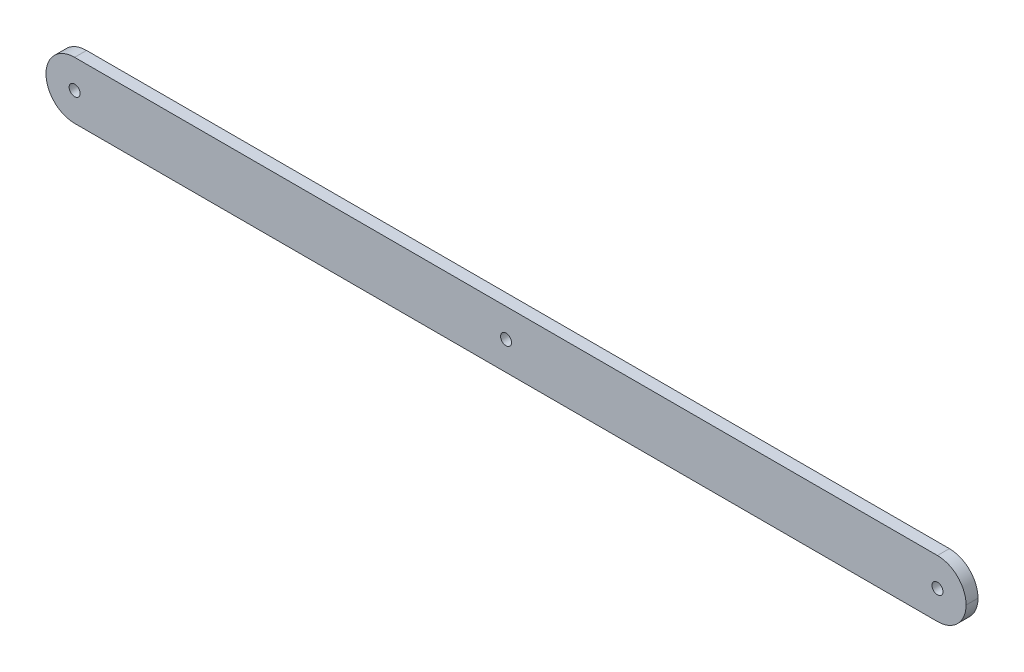
SolidWorks part; units mm, degrees
material "Acrylic (Medium-high impact)"
ref_plane "Front Plane" through (0, 0, 0) normal (0, 0, 1) x (1, 0, 0)
ref_plane "Top Plane" through (0, 0, 0) normal (0, 1, 0) x (1, 0, 0)
ref_plane "Right Plane" through (0, 0, 0) normal (1, 0, 0) x (0, 0, -1)
sketch "Sketch1" plane through (0, 0, 0) normal (0, 0, 1) x (1, 0, 0)
  line L1 (-122.555, -7.62) -> (122.555, -7.62)
  line L2 (-122.555, -7.62) -> (-122.555, 7.62)
  line L3 (-122.555, 7.62) -> (122.555, 7.62)
  line L4 (122.555, -7.62) -> (122.555, 7.62)
  line L5 (-122.555, -7.62) -> (122.555, 7.62) construction
  line L6 (-122.555, 7.62) -> (122.555, -7.62) construction
  point P0 (0, 0)
  dimension "D1" = 245.11
  dimension "D2" = 15.24
extrude "Boss-Extrude1" add sketch "Sketch1" along normal blind 3.175
fillet "Fillet2" radius 7.62 4 edges at (-122.555, -7.62, 1.5875) (-122.555, 7.62, 1.5875) (122.555, -7.62, 1.5875) (122.555, 7.62, 1.5875)
sketch "Sketch3" plane through (0, 0, 3.175) normal (0, 0, 1) x (1, 0, 0)
  circle A0 centre (-114.935, 0) radius 1.4605
  circle A1 centre (114.935, 0) radius 1.4605
  circle A2 centre (0, 0) radius 1.4605
  dimension "D1" = 2.921
  dimension "D2" = 2.921
  dimension "D3" = 2.921
extrude "Cut-Extrude1" cut sketch "Sketch3" against normal through all
